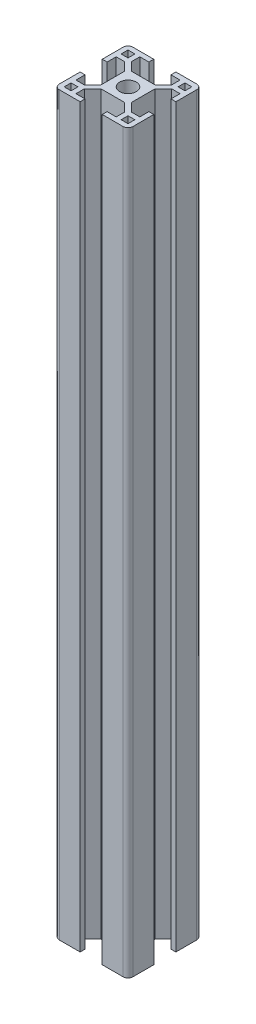
SolidWorks part; units mm, degrees
ref_plane "Front plane" through (0, 0, 0) normal (0, 0, 1) x (1, 0, 0)
ref_plane "Top plane" through (0, 0, 0) normal (0, 1, 0) x (1, 0, 0)
ref_plane "Right plane" through (0, 0, 0) normal (1, 0, 0) x (0, 0, -1)
ref_axis "Axis X" through (0, 0, 0) along (1, 0, 0)
ref_axis "Axis Y" through (0, 0, 0) along (0, 1, 0)
ref_axis "Axis Z" through (0, 0, 0) along (0, 0, 1)
sketch "Sketch1" plane through (0, 0, 0) normal (0, 1, 0) x (1, 0, 0)
  line L1 (-10, 10) -> (10, 10)
  line L2 (-10, 10) -> (-10, -10)
  line L3 (-10, -10) -> (10, -10)
  line L4 (10, 10) -> (10, -10)
  line L5 (-10, 10) -> (10, -10) construction
  line L6 (-10, -10) -> (10, 10) construction
  point P0 (0, 0)
  dimension "D2" = 20
extrude "Extrude1" add sketch "Sketch1" along normal blind 200
sketch "Sketch2" plane through (0, 200, 0) normal (0, 1, 0) x (1, 0, 0)
  line L0 (0, 0) -> (10, 0) construction
  line L1 (10, -10) -> (10, 10) construction
  line L2 (10, 10) -> (-10, 10) construction
  line L3 (8.6667, 3) -> (11.3333, 3)
  line L4 (8.6667, 3) -> (8.6667, -3) construction
  line L5 (8.6667, -3) -> (11.3333, -3)
  line L6 (11.3333, 3) -> (11.3333, -3)
  line L7 (8.6667, 3) -> (11.3333, -3) construction
  line L8 (8.6667, -3) -> (11.3333, 3) construction
  line L9 (6.8, 8.6667) -> (8.6667, 8.6667)
  line L10 (6.8, 8.6667) -> (6.8, 6.8)
  line L11 (6.8, 6.8) -> (8.6667, 6.8)
  line L12 (8.6667, 8.6667) -> (8.6667, 6.8)
  line L13 (6.8, 8.6667) -> (8.6667, 6.8) construction
  line L14 (6.8, 6.8) -> (8.6667, 8.6667) construction
  line L15 (0, 0) -> (10, 10) construction
  line L16 (8.6667, 3) -> (8.6667, 5.4667)
  line L17 (8.6667, 5.4667) -> (6.4095, 5.4667)
  line L18 (6.4095, 5.4667) -> (4.1333, 3.1905)
  line L19 (4.1333, 3.1905) -> (4.1333, -3.1905)
  line L20 (4.1333, -3.1905) -> (6.4095, -5.4667)
  line L21 (6.4095, -5.4667) -> (8.6667, -5.4667)
  line L22 (8.6667, -5.4667) -> (8.6667, -3)
  line L65 (-3.1905, 4.1333) -> (-5.4667, 6.4095)
  line L66 (-5.4667, 6.4095) -> (-5.4667, 8.6667)
  line L67 (-5.4667, 8.6667) -> (-3, 8.6667)
  line L68 (3, 11.3333) -> (-3, 11.3333)
  line L69 (-3, 8.6667) -> (-3, 11.3333)
  line L70 (3, 8.6667) -> (3, 11.3333)
  line L71 (3, 8.6667) -> (5.4667, 8.6667)
  line L72 (5.4667, 8.6667) -> (5.4667, 6.4095)
  line L73 (5.4667, 6.4095) -> (3.1905, 4.1333)
  line L74 (3.1905, 4.1333) -> (-3.1905, 4.1333)
  line L75 (0, 10) -> (0, -10) construction
  line L76 (-10, -10) -> (10, -10) construction
  line L77 (0, 0) -> (-10, 0) construction
  line L78 (-10, 10) -> (-10, -10) construction
  line L79 (8.6667, -8.6667) -> (8.6667, -6.8)
  line L80 (6.8, -6.8) -> (8.6667, -6.8)
  line L81 (6.8, -8.6667) -> (6.8, -6.8)
  line L82 (6.8, -8.6667) -> (8.6667, -8.6667)
  line L83 (-6.8, 6.8) -> (-8.6667, 6.8)
  line L84 (-8.6667, 8.6667) -> (-8.6667, 6.8)
  line L85 (-6.8, 8.6667) -> (-8.6667, 8.6667)
  line L86 (-6.8, 8.6667) -> (-6.8, 6.8)
  line L87 (-6.8, -8.6667) -> (-8.6667, -8.6667)
  line L88 (-6.8, -8.6667) -> (-6.8, -6.8)
  line L89 (-6.8, -6.8) -> (-8.6667, -6.8)
  line L90 (-8.6667, -8.6667) -> (-8.6667, -6.8)
  line L91 (-6.4095, -5.4667) -> (-8.6667, -5.4667)
  line L92 (-4.1333, -3.1905) -> (-6.4095, -5.4667)
  line L93 (-4.1333, 3.1905) -> (-4.1333, -3.1905)
  line L94 (-6.4095, 5.4667) -> (-4.1333, 3.1905)
  line L95 (-8.6667, 5.4667) -> (-6.4095, 5.4667)
  line L96 (-8.6667, 3) -> (-8.6667, 5.4667)
  line L97 (-8.6667, 3) -> (-11.3333, 3)
  line L98 (-11.3333, 3) -> (-11.3333, -3)
  line L99 (-8.6667, -3) -> (-11.3333, -3)
  line L100 (-8.6667, -5.4667) -> (-8.6667, -3)
  line L101 (3.1905, -4.1333) -> (-3.1905, -4.1333)
  line L102 (5.4667, -6.4095) -> (3.1905, -4.1333)
  line L103 (5.4667, -8.6667) -> (5.4667, -6.4095)
  line L104 (3, -8.6667) -> (5.4667, -8.6667)
  line L105 (3, -8.6667) -> (3, -11.3333)
  line L106 (3, -11.3333) -> (-3, -11.3333)
  line L107 (-3, -8.6667) -> (-3, -11.3333)
  line L108 (-5.4667, -8.6667) -> (-3, -8.6667)
  line L109 (-5.4667, -6.4095) -> (-5.4667, -8.6667)
  line L110 (-3.1905, -4.1333) -> (-5.4667, -6.4095)
  circle A0 centre (0, 0) radius 2.2667
  point P9 (7.7333, 7.7333)
  point P20 (7.5381, 5.4667)
  point P27 (10, -3)
  point P34 (-3, 10)
  point P37 (5.4667, 7.5381)
  dimension "D10" = 4.5333
  dimension "D1" = 2.6667
  dimension "D2" = 6
  dimension "D3" = 1.3333
  dimension "D4" = 1.3333
  dimension "D5" = 4.5333
  dimension "D6" = 5.4667
  dimension "D7" = 0.6667
  dimension "D8" = 1.3333
extrude "Extrude2" cut sketch "Sketch2" against normal through all
fillet "Fillet1" radius 1.3333 4 edges at (10, 100, 10) (10, 100, -10) (-10, 100, 10) (-10, 100, -10)
sketch "Эскиз1" plane through (10, 0, 0) normal (1, 0, 0) x (0, 0, -1)
  line L0 (0, 0) -> (0, 200) construction
  line L1 (3.1905, 200) -> (-3.1905, 200) construction
  line L2 (0, 50) -> (-56.213, 50) construction
  line L3 (-8.6667, 0) -> (-3, 0) construction
  circle A0 centre (0, 43) radius 2.5
  circle A1 centre (0, 57) radius 2.5
  dimension "D1" = 5
  dimension "D2" = 14
  dimension "D3" = 50
extrude "Вырез-Вытянуть1" cut sketch "Эскиз1" against normal through all
equation "\"prof_width\"= 20'Aluminium profile parameters"
equation "\"D1@Sketch1\"=\"prof_width\""
equation "\"D2@Sketch1\"=\"prof_width\""
equation "\"prof_groove\"= 6"
equation "\"prof_length\"= 200"
equation "\"D1@Extrude1\"=\"prof_length\""
equation "\"D1@Sketch2\"=\"prof_width\"/30*4"
equation "\"D2@Sketch2\"=\"prof_groove\""
equation "\"D3@Sketch2\"=\"D1@Sketch2\"/2"
equation "\"D4@Sketch2\"=\"D3@Sketch2\""
equation "\"D5@Sketch2\"=\"prof_width\"/30*6.8"
equation "\"D6@Sketch2\"=\"prof_width\"/30*8.2"
equation "\"D7@Sketch2\"=\"D3@Sketch2\"/2"
equation "\"D8@Sketch2\"=\"D3@Sketch2\""
equation "\"D10@Sketch2\"=\"prof_width\"/30*6.8"
equation "\"D1@Fillet1\"=\"prof_width\"/30*2"
